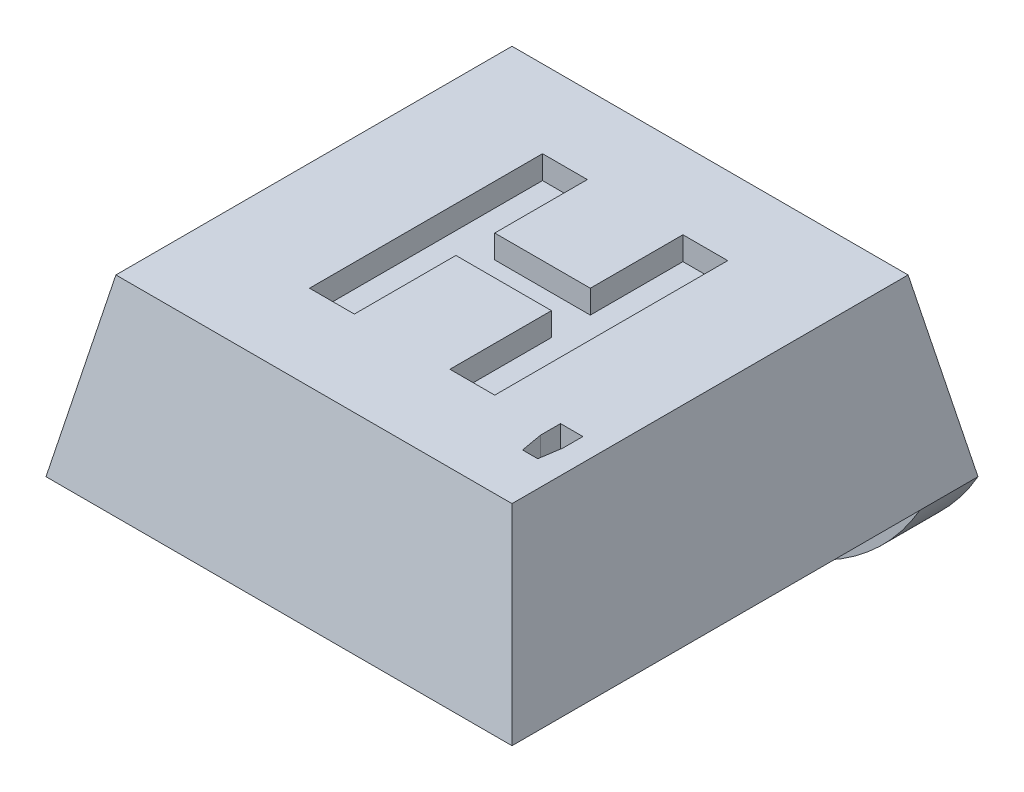
SolidWorks part; units mm, degrees
ref_plane "Front Plane" through (0, 0, 0) normal (0, 0, 1) x (1, 0, 0)
ref_plane "Top Plane" through (0, 0, 0) normal (0, 1, 0) x (1, 0, 0)
ref_plane "Right Plane" through (0, 0, 0) normal (1, 0, 0) x (0, 0, -1)
sketch "Sketch1" plane through (0, 0, 0) normal (0, 1, 0) x (1, 0, 0)
  line L1 (0, 0) -> (8, 0)
  line L2 (0, 0) -> (0, 8)
  line L3 (0, 8) -> (8, 8)
  line L4 (8, 0) -> (8, 8)
  dimension "D1" = 8
  dimension "D2" = 8
extrude "Boss-Extrude1" add sketch "Sketch1" along normal blind 3
sketch "Sketch2" plane through (0, 0, 0) normal (0, 0, 1) x (1, 0, 0)
  line L0 (0, 0) -> (0.6, 3)
  line L1 (0, 3) -> (8, 3) construction
  line L2 (0.6, 3) -> (0, 3)
  line L3 (0, 3) -> (0, 0)
  line L4 (8, 0) -> (7.4, 3)
  line L5 (7.4, 3) -> (8, 3)
  line L6 (8, 3) -> (8, 0)
  dimension "D1" = 0.6
  dimension "D2" = 0.6
extrude "Cut-Extrude1" cut sketch "Sketch2" against normal through all both and the other way through all
sketch "Sketch3" plane through (0, 0, 0) normal (1, 0, 0) x (0, 0, -1)
  line L0 (0, 0) -> (0.6, 3)
  line L1 (8, 3) -> (0, 3) construction
  line L2 (0.6, 3) -> (0, 3)
  line L3 (0, 3) -> (0, 0)
  line L4 (8, 3) -> (7.4, 3)
  line L5 (7.4, 3) -> (8, 0)
  line L6 (8, 3) -> (8, 0)
  dimension "D1" = 0.6
  dimension "D2" = 0.6
extrude "Cut-Extrude2" cut sketch "Sketch3" along normal blind 11
sketch "Sketch4" plane through (0, 0, 0) normal (0, -1, 0) x (1, 0, 0)
  line L0 (8, 0) -> (8, -8) construction
  line L3 (0, 0) -> (8, 0) construction
  circle A0 centre (4, -3.75) radius 1.75
  dimension "D1" = 3.5
  dimension "D2" = 4
  dimension "D3" = 3.75
extrude "Cut-Extrude3" cut sketch "Sketch4" against normal blind 0.4
sketch "Sketch5" plane through (0, 0, 0) normal (0, -1, 0) x (1, 0, 0)
  line L0 (8, 0) -> (8, -8) construction
  line L1 (0, -8) -> (8, -8)
  line L2 (0, -8) -> (0, -7)
  line L3 (0, -7) -> (8, -7)
  line L4 (8, -8) -> (8, -7)
  dimension "D1" = 1
extrude "Boss-Extrude2" add sketch "Sketch5" along normal blind 2
fillet "Fillet1" radius 4 2 edges at (8, -2, -7.5) (0, -2, -7.5)
sketch "Sketch6" plane through (0, 3, 0) normal (0, 1, 0) x (1, 0, 0)
  text T0 "H" font "Arial" height 4
extrude "Cut-Extrude4" cut sketch "Sketch6" against normal blind 0.4
sketch "Sketch7" plane through (0, 3, 0) normal (0, 1, 0) x (1, 0, 0)
  text T0 "'" font "Arial" height 2
extrude "Cut-Extrude5" cut sketch "Sketch7" against normal blind 0.5
